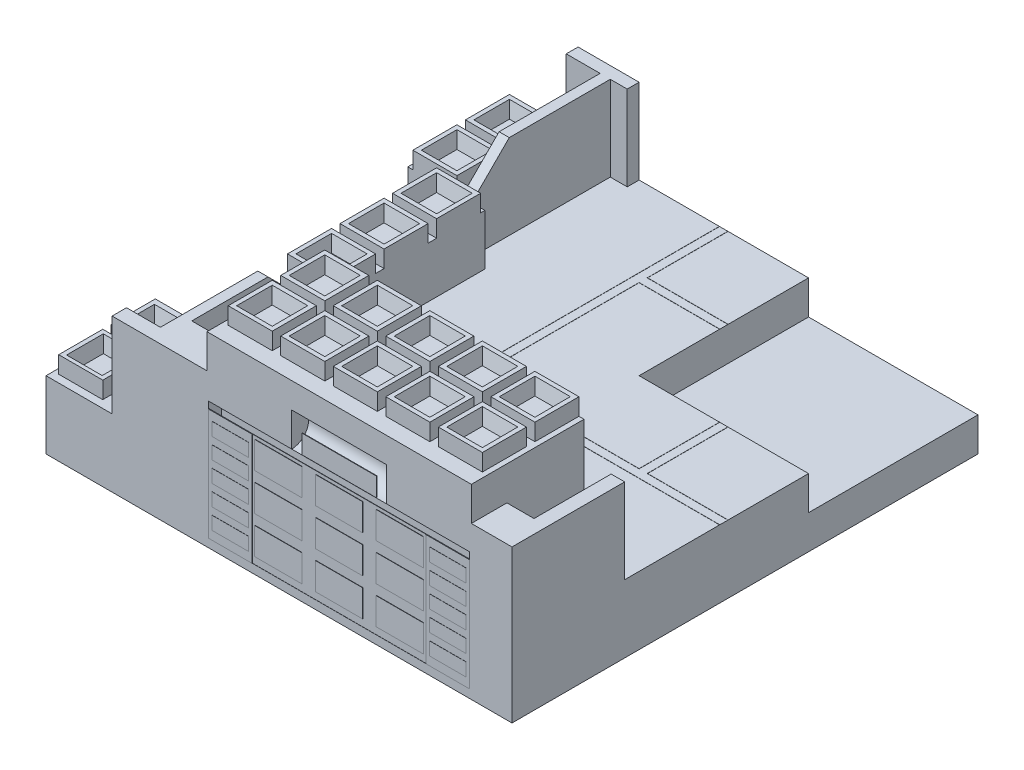
SolidWorks part; units mm, degrees
material "1023 碳钢板 (SS)"
ref_plane "前视基准面" through (0, 0, 0) normal (0, 0, 1) x (1, 0, 0)
ref_plane "上视基准面" through (0, 0, 0) normal (0, 1, 0) x (1, 0, 0)
ref_plane "右视基准面" through (0, 0, 0) normal (1, 0, 0) x (0, 0, -1)
sketch "草图1" plane through (0, 0, 0) normal (0, 1, 0) x (1, 0, 0)
  line L1 (1375, -1375) -> (-1375, -1375)
  line L2 (1375, -1375) -> (1375, 1375)
  line L3 (1375, 1375) -> (-1375, 1375)
  line L4 (-1375, -1375) -> (-1375, 1375)
  line L5 (1375, -1375) -> (-1375, 1375) construction
  line L6 (1375, 1375) -> (-1375, -1375) construction
  point P0 (0, 0)
  dimension "D1" = 2750
  dimension "D2" = 2750
extrude "凸台-拉伸1" add sketch "草图1" along normal blind 200
sketch "草图2" plane through (0, 200, 0) normal (0, 1, 0) x (1, 0, 0)
  line L1 (1375, 1375) -> (375, 1375)
  line L2 (1375, 1375) -> (1375, 375)
  line L3 (1375, 375) -> (375, 375)
  line L4 (375, 1375) -> (375, 375)
  line L8 (-1375, 1375) -> (-1375, -1375)
  line L9 (-1375, -1375) -> (1375, -1375)
  line L10 (1375, -1375) -> (1375, 1375)
  line L11 (1375, 1375) -> (-1375, 1375)
  line L12 (-1375, 1375) -> (-1375, -1375)
  line L13 (-1375, -1375) -> (1375, -1375)
  line L14 (1375, -1375) -> (1375, 1375)
  line L15 (1375, 1375) -> (-1375, 1375)
  line M9 (-1375, 1375) -> (-1375, -1375)
  line M10 (-1375, -1375) -> (1375, -1375)
  line M11 (1375, -1375) -> (1375, 1375)
  line M12 (1375, 1375) -> (-1375, 1375)
  dimension "D1" = 1000
  dimension "D2" = 1000
  dimension "D3" = 0
extrude "凸台-拉伸2" add sketch "草图2" along normal blind 200 contours L4 L3 M12 M9 M10 M11 region at (-133.3333, 200, 133.3333)
sketch "草图4" plane through (0, 0, 0) normal (0, -1, 0) x (1, 0, 0)
  line L0 (-1375, -1375) -> (-1375, 1375) construction
  line L1 (-1375, -760) -> (-885, -760)
  line L2 (-1375, -760) -> (-1375, 760)
  line L3 (-1375, 760) -> (-885, 760)
  line L4 (-885, -760) -> (-885, 760)
  line L5 (-1375, -760) -> (-885, 760) construction
  line L6 (-1375, 760) -> (-885, -760) construction
  line L7 (-1375, 1375) -> (1375, 1375) construction
  point P0 (-1130, 0)
  dimension "D1" = 615
  dimension "D2" = 490
extrude "切除-拉伸2" cut sketch "草图4" against normal blind 1200
sketch "草图6" plane through (0, 400, 0) normal (0, 1, 0) x (1, 0, 0)
  line L0 (-625, 1375) -> (-625, -625) construction
  line L1 (375, 1375) -> (-1375, 1375) construction
  line L2 (-625, -625) -> (1375, -625) construction
  line L3 (-1375, -760) -> (-885, -760) construction
  line L4 (375, 1375) -> (375, 375) construction
  line L5 (-1085, -1020) -> (-1345, -1020)
  line L6 (-1085, -1020) -> (-1085, -760)
  line L7 (-1085, -760) -> (-1345, -760)
  line L8 (1375, 375) -> (375, 375) construction
  line L9 (-885, -760) -> (-885, 760) construction
  line L10 (-1375, 1375) -> (-1375, 760) construction
  line L11 (-885, 760) -> (-1375, 760) construction
  line L12 (-1085, 1020) -> (-1345, 1020)
  line L13 (-1085, 1020) -> (-1085, 760)
  line L14 (-1085, 760) -> (-1345, 760)
  line L15 (-1345, 1020) -> (-1345, 760)
  line L16 (-1085, 1020) -> (-1345, 760) construction
  line L17 (-1085, 760) -> (-1345, 1020) construction
  line L18 (-1345, -1020) -> (-1345, -760)
  line L19 (-1110, 995) -> (-1320, 995)
  line L20 (-1110, 995) -> (-1110, 785)
  line L21 (-1110, 785) -> (-1320, 785)
  line L22 (-1320, 995) -> (-1320, 785)
  line L23 (-1110, 995) -> (-1320, 785) construction
  line L24 (-1110, 785) -> (-1320, 995) construction
  line L25 (-1085, -1020) -> (-1345, -760) construction
  line L26 (-1375, 1045) -> (-927.1578, 1045) construction
  line L27 (-1085, 1070) -> (-1345, 1330) construction
  line L28 (-1085, 1330) -> (-1345, 1070) construction
  line L29 (-1110, 1305) -> (-1320, 1305)
  line L30 (-1085, 1330) -> (-1345, 1330)
  line L31 (-1110, 1305) -> (-1320, 1095) construction
  line L32 (-1110, 1095) -> (-1320, 1305) construction
  line L33 (-1320, 1095) -> (-1320, 1305)
  line L34 (-1110, 1095) -> (-1110, 1305)
  line L35 (-1110, 1095) -> (-1320, 1095)
  line L36 (-1345, 1070) -> (-1345, 1330)
  line L37 (-1085, 1070) -> (-1085, 1330)
  line L38 (-1085, 1070) -> (-1345, 1070)
  line L39 (-1085, -760) -> (-1345, -1020) construction
  line L41 (-755, 1375) -> (-755, -1375) construction
  line L42 (-1375, -1375) -> (1375, -1375) construction
  line L43 (-885, 0) -> (-625, 0) construction
  line L44 (-1085, -1070) -> (-1345, -1070)
  line L45 (-1085, -1070) -> (-1085, -1330)
  line L46 (-1085, -1330) -> (-1345, -1330)
  line L47 (-1345, -1070) -> (-1345, -1330)
  line L48 (-1085, -1070) -> (-1345, -1330) construction
  line L49 (-1085, -1330) -> (-1345, -1070) construction
  line L50 (-1375, -760) -> (-1375, -1375) construction
  point P13 (-1215, 890)
  point P20 (-1215, 890)
  point P32 (-1215, 1200)
  point P33 (-1215, -890)
  point P46 (-755, 0)
  point P51 (-1215, -1200)
  dimension "D1" = 1000
  dimension "D2" = 1000
  dimension "D3" = 200
  dimension "D4" = 30
  dimension "D5" = 260
  dimension "D6" = 210
  dimension "D7" = 310
  dimension "D8" = 260
  dimension "D9" = 30
  dimension "D10" = 310
extrude "凸台-拉伸3" add sketch "草图6" along normal blind 100 contours L38 L36 L30 L37
extrude "凸台-拉伸4" add sketch "草图6<4>" along normal blind 100 contours L13 L14 L15 L12 | L6 L5 L18 L7 | L45 L44 L47 L46
sketch "草图6<4>" plane through (0, 400, 0) normal (0, 1, 0) x (1, 0, 0) same geometry as "草图6"
sketch "草图7" plane through (0, 500, 0) normal (0, 1, 0) x (1, 0, 0)
  line L0 (-1345, 1070) -> (-1345, 1330) construction
  line L1 (-1320, 1095) -> (-1110, 1095)
  line L2 (-1320, 1095) -> (-1320, 1305)
  line L3 (-1320, 1305) -> (-1110, 1305)
  line L4 (-1110, 1095) -> (-1110, 1305)
  line L5 (-1320, 1095) -> (-1110, 1305) construction
  line L6 (-1320, 1305) -> (-1110, 1095) construction
  line L7 (-1085, 1070) -> (-1345, 1070) construction
  line L8 (-1320, 785) -> (-1110, 785)
  line L9 (-1320, 785) -> (-1320, 995)
  line L10 (-1320, 995) -> (-1110, 995)
  line L11 (-1110, 785) -> (-1110, 995)
  line L12 (-1320, 785) -> (-1110, 995) construction
  line L13 (-1320, 995) -> (-1110, 785) construction
  line L14 (-1085, 1020) -> (-1085, 760) construction
  line L15 (-1085, 1020) -> (-1345, 1020) construction
  line L16 (-1345, -890) -> (-1085, -890) construction
  line L17 (-1110, -989.9712) -> (-1320, -989.9712)
  line L18 (-1110, -989.9712) -> (-1110, -790.0288)
  line L19 (-1110, -790.0288) -> (-1320, -790.0288)
  line L20 (-1320, -989.9712) -> (-1320, -790.0288)
  line L21 (-1110, -989.9712) -> (-1320, -790.0288) construction
  line L22 (-1110, -790.0288) -> (-1320, -989.9712) construction
  line L23 (-1110, -1308.4435) -> (-1320, -1308.4435)
  line L24 (-1110, -1308.4435) -> (-1110, -1091.5565)
  line L25 (-1110, -1091.5565) -> (-1320, -1091.5565)
  line L26 (-1320, -1308.4435) -> (-1320, -1091.5565)
  line L27 (-1110, -1308.4435) -> (-1320, -1091.5565) construction
  line L28 (-1110, -1091.5565) -> (-1320, -1308.4435) construction
  line L29 (-1345, -1020) -> (-1345, -760) construction
  line L30 (-1085, -1020) -> (-1085, -760) construction
  line L31 (-1345, -1200) -> (-1085, -1200) construction
  line L32 (-1085, -760) -> (-1345, -760) construction
  line L33 (-1215, -760) -> (-1215, -1020) construction
  line L34 (-1085, -1020) -> (-1345, -1020) construction
  line L35 (-1345, -1070) -> (-1345, -1330) construction
  line L36 (-1085, -1070) -> (-1085, -1330) construction
  line L37 (-1215, -1070) -> (-1215, -1330) construction
  line L38 (-1085, -1070) -> (-1345, -1070) construction
  line L39 (-1085, -1330) -> (-1345, -1330) construction
  point P0 (-1215, 1200)
  point P5 (-1215, -890)
  point P8 (-1345, 1200)
  point P11 (-1215, 1070)
  point P16 (-1215, 890)
  point P19 (-1085, 890)
  point P22 (-1215, 1020)
  point P27 (-1215, -1200)
  point P38 (-1215, -890)
  point P57 (-1215, -1200)
  dimension "D1" = 210
  dimension "D2" = 210
extrude "切除-拉伸3" cut sketch "草图7" against normal blind 80 draft 15 contours L8 L11 L10 L9 | L1 L4 L3 L2 | L8 L11 L10 L9 | L18 L17 L20 L19 | L24 L23 L26 L25 region at (-1215, 500, -1200) region at (-1215, 500, -890)
sketch "草图8" plane through (0, 400, 0) normal (0, 1, 0) x (1, 0, 0)
  line L0 (-885, 0) -> (-625, 0) construction
  line L1 (-885, -760) -> (-885, 760) construction
  line L3 (-625, 1375) -> (-625, -1375) construction
  line L4 (375, 1375) -> (-1375, 1375) construction
  line L5 (-1375, -1375) -> (1375, -1375) construction
  line L6 (375, 1375) -> (375, 375) construction
  line L7 (-755, 457.7919) -> (-755, -449.0399) construction
  line L9 (-625, -130) -> (-885, -130)
  line L10 (-625, -130) -> (-625, 130)
  line L11 (-625, 130) -> (-885, 130)
  line L12 (-885, -130) -> (-885, 130)
  line L13 (-625, -130) -> (-885, 130) construction
  line L14 (-625, 130) -> (-885, -130) construction
  line L15 (-625, -440) -> (-885, -440)
  line L16 (-625, -440) -> (-625, -180)
  line L17 (-625, -180) -> (-885, -180)
  line L18 (-885, -440) -> (-885, -180)
  line L19 (-625, -440) -> (-885, -180) construction
  line L20 (-625, -180) -> (-885, -440) construction
  line L21 (-625, 440) -> (-885, 440)
  line L22 (-625, 440) -> (-625, 180)
  line L23 (-625, 180) -> (-885, 180)
  line L24 (-885, 440) -> (-885, 180)
  line L25 (-625, 440) -> (-885, 180) construction
  line L26 (-625, 180) -> (-885, 440) construction
  point P4 (-755, 0)
  point P17 (-755, 0)
  point P21 (-755, -310)
  point P26 (-755, 310)
  dimension "D1" = 1000
  dimension "D2" = 310
  dimension "D3" = 310
extrude "凸台-拉伸5" add sketch "草图8" along normal blind 400
sketch "草图9" plane through (0, 800, 0) normal (0, 1, 0) x (1, 0, 0)
  line L0 (-885, 440) -> (-625, 180)
  line L1 (-625, 440) -> (-885, 180)
  line L2 (-885, 130) -> (-625, -130)
  line L3 (-625, 130) -> (-885, -130)
  line L4 (-625, -180) -> (-885, -440)
  line L5 (-885, -180) -> (-625, -440)
  line L7 (-650, 205) -> (-860, 205)
  line L8 (-650, 205) -> (-650, 415)
  line L9 (-650, 415) -> (-860, 415)
  line L10 (-860, 205) -> (-860, 415)
  line L11 (-650, 205) -> (-860, 415) construction
  line L12 (-650, 415) -> (-860, 205) construction
  line L13 (-650, -105) -> (-860, -105)
  line L14 (-650, -105) -> (-650, 105)
  line L15 (-650, 105) -> (-860, 105)
  line L16 (-860, -105) -> (-860, 105)
  line L17 (-650, -105) -> (-860, 105) construction
  line L18 (-650, 105) -> (-860, -105) construction
  line L19 (-650, -415) -> (-860, -415)
  line L20 (-650, -415) -> (-650, -205)
  line L21 (-650, -205) -> (-860, -205)
  line L22 (-860, -415) -> (-860, -205)
  line L23 (-650, -415) -> (-860, -205) construction
  line L24 (-650, -205) -> (-860, -415) construction
  point P24 (-755, 310)
  point P29 (-755, 0)
  point P34 (-755, -310)
  dimension "D1" = 210
extrude "切除-拉伸4" cut sketch "草图9" against normal blind 80 draft 15 contours L8 L9 L10 L7 | L14 L15 L16 L13 | L20 L21 L22 L19
sketch "草图11" plane through (0, 400, 0) normal (0, 1, 0) x (1, 0, 0)
  line L0 (-625, -180) -> (-885, -180) construction
  line L1 (-625, -180) -> (-625, -130)
  line L2 (-625, -440) -> (-625, -180) construction
  line L3 (-885, -130) -> (-625, -130) construction
  line L4 (-625, 180) -> (-625, 130)
  line L5 (-625, 180) -> (-625, 440) construction
  line L6 (-885, 180) -> (-625, 180) construction
  line L7 (-625, -130) -> (-625, 130) construction
  line L8 (-625, 130) -> (-885, 130) construction
  line L9 (-885, 180) -> (-885, 130)
  line L10 (-885, 130) -> (-885, 180) construction
  line L11 (-885, 130) -> (-625, 130)
  line L12 (-625, 180) -> (-885, 180)
  line L13 (-885, -130) -> (-625, -130)
  line L14 (-885, -180) -> (-885, -130) construction
  line L15 (-625, -180) -> (-885, -180)
  line L16 (-885, -180) -> (-885, -130)
extrude "凸台-拉伸7" add sketch "草图11" along normal blind 300
sketch "草图14" plane through (0, 400, 0) normal (0, 1, 0) x (1, 0, 0)
  line L0 (-985, 1375) -> (-985, 1305)
  line L1 (375, 1375) -> (-1375, 1375) construction
  line L2 (-785, 1305) -> (-985, 1305)
  line L3 (-785, 1305) -> (-785, 465)
  line L4 (-785, 465) -> (-885, 465)
  line L5 (-885, 440) -> (-885, 760) construction
  line L6 (-1375, 1375) -> (-1375, 760) construction
  line L7 (-625, 440) -> (-885, 440) construction
  line L8 (-625, 440) -> (-625, 552.5193)
  line L9 (-625, -440) -> (-625, 440) construction
  line L10 (-625, 180) -> (-625, 440) construction
  line L11 (-625, 465) -> (-725, 465)
  line L12 (-725, 465) -> (-725, 1305)
  line L13 (-725, 1305) -> (-625, 1305)
  line L14 (-625, 1305) -> (-625, 1375)
  line L15 (-625, 1375) -> (-985, 1375)
  line L16 (-625, 440) -> (-885, 440)
  line L17 (-885, 440) -> (-885, 180) construction
  line L18 (-625, 440) -> (-885, 440) construction
  line L19 (-885, 440) -> (-885, 465)
  line M9 (-885, 440) -> (-625, 440)
  line M23 (375, 1375) -> (-1375, 1375)
  line M30 (-885, 760) -> (-885, 440)
  dimension "D1" = 390
  dimension "D2" = 70
  dimension "D3" = 25
  dimension "D4" = 100
extrude "凸台-拉伸9" add sketch "草图14" along normal blind 500 contours L13 L14 L0 L2 L3 L4 L8 L11 L12 M23 M30 M9 region at (-770.3471, 400, -990.4172)
sketch "草图15" plane through (-625, 0, 0) normal (1, 0, 0) x (0, 0, -1)
  line L0 (440, 800) -> (440, 700)
  line L1 (440, 900) -> (440, 800) construction
  line L2 (440, 700) -> (465, 700)
  line L3 (465, 900) -> (465, 400) construction
  line L4 (465, 700) -> (465, 900)
  line L5 (465, 900) -> (465, 400) construction
  line L6 (440, 900) -> (465, 900) construction
  line L7 (465, 900) -> (440, 900)
  line L8 (440, 900) -> (440, 800)
extrude "切除-拉伸5" cut sketch "草图15" against normal through all
sketch "草图16" plane through (-725, 0, 0) normal (1, 0, 0) x (0, 0, -1)
  line L0 (465, 700) -> (508.8251, 700)
  line L1 (465, 700) -> (465, 400) construction
  line L2 (465, 900) -> (465, 700) construction
  line L3 (508.8251, 700) -> (708.8251, 900)
  line L4 (465, 900) -> (1305, 900) construction
  line L5 (708.8251, 900) -> (465, 900)
  line L6 (465, 900) -> (465, 700)
  dimension "D1" = 45
  dimension "D2" = 200
extrude "切除-拉伸6" cut sketch "草图16" against normal through all
sketch "草图18" plane through (0, 400, 0) normal (0, 1, 0) x (1, 0, 0)
  line L0 (-885, -465) -> (-785, -465)
  line L1 (-885, -760) -> (-885, -440) construction
  line L2 (-785, -465) -> (-785, -1290)
  line L3 (-785, -1290) -> (-985, -1290)
  line L4 (-985, -1290) -> (-985, -1375)
  line L5 (-1375, -1375) -> (1375, -1375) construction
  line L6 (-1375, -760) -> (-1375, -1375) construction
  line L7 (-885, -440) -> (-625, -440) construction
  line L8 (-885, -440) -> (-625, -440)
  line L9 (-625, -440) -> (-625, -465)
  line L10 (-625, -465) -> (-725, -465)
  line L11 (-725, -465) -> (-725, -1165)
  line L12 (-725, -1165) -> (-425, -1165)
  line L13 (-425, -1165) -> (-425, -1375)
  line L14 (-425, -1375) -> (-985, -1375)
  line L15 (-625, -440) -> (-625, 465) construction
  line L16 (-885, -440) -> (-885, -465)
  dimension "D1" = 390
  dimension "D2" = 25
  dimension "D3" = 100
  dimension "D4" = 200
  dimension "D5" = 850
  dimension "D6" = 160
  dimension "D7" = 210
extrude "凸台-拉伸10" add sketch "草图18" along normal blind 500
sketch "草图19" plane through (-625, 0, 0) normal (1, 0, 0) x (0, 0, -1)
  line L0 (-440, 800) -> (-440, 700)
  line L1 (-440, 800) -> (-180, 800) construction
  line L2 (-440, 900) -> (-440, 800) construction
  line L3 (-440, 700) -> (-465, 700)
  line L4 (-465, 900) -> (-465, 400) construction
  line L5 (-465, 700) -> (-465, 900)
  line L6 (-465, 900) -> (-440, 900)
  line L7 (-465, 900) -> (-440, 900) construction
  line L8 (-440, 900) -> (-440, 800)
extrude "切除-拉伸7" cut sketch "草图19" against normal through all
sketch "草图20" plane through (-725, 0, 0) normal (1, 0, 0) x (0, 0, -1)
  line L0 (-465, 700) -> (-515, 700)
  line L1 (-465, 900) -> (-465, 700) construction
  line L2 (-465, 700) -> (-465, 400) construction
  line L3 (-515, 700) -> (-715, 900)
  line L4 (-1165, 900) -> (-465, 900) construction
  line L5 (-715, 900) -> (-465, 900)
  line L6 (-465, 900) -> (-465, 700)
  dimension "D1" = 200
  dimension "D2" = 45
  dimension "D3" = 50
extrude "切除-拉伸8" cut sketch "草图20" against normal through all
sketch "草图28" plane through (0, 400, 0) normal (0, 1, 0) x (1, 0, 0)
  line L0 (-425, -1375) -> (-425, -710)
  line L1 (-425, -710) -> (1105, -710)
  line L2 (1105, -710) -> (1105, -1375)
  line L3 (-265, -765.1076) -> (-265, -988.6758) construction
  line L4 (1375, -1375) -> (1375, 375) construction
  line L5 (-625, -465) -> (-625, 465) construction
  line L6 (-725, -465) -> (-625, -465) construction
  line L7 (175, -969.7166) -> (-85, -709.7166) construction
  line L8 (-135, -969.7166) -> (-395, -969.7166)
  line L9 (-135, -969.7166) -> (-135, -709.7166)
  line L10 (-135, -709.7166) -> (-395, -709.7166)
  line L11 (-395, -969.7166) -> (-395, -709.7166)
  line L12 (-135, -969.7166) -> (-395, -709.7166) construction
  line L13 (-135, -709.7166) -> (-395, -969.7166) construction
  line L14 (175, -709.7166) -> (-85, -969.7166) construction
  line L15 (175, -969.7166) -> (175, -709.7166)
  line L16 (175, -969.7166) -> (-85, -969.7166)
  line L17 (-85, -969.7166) -> (-85, -709.7166)
  line L18 (175, -709.7166) -> (-85, -709.7166)
  line L19 (485, -969.7166) -> (225, -709.7166) construction
  line L20 (485, -709.7166) -> (225, -969.7166) construction
  line L21 (485, -969.7166) -> (485, -709.7166)
  line L22 (485, -969.7166) -> (225, -969.7166)
  line L23 (225, -969.7166) -> (225, -709.7166)
  line L24 (485, -709.7166) -> (225, -709.7166)
  line L25 (795, -969.7166) -> (535, -709.7166) construction
  line L26 (795, -709.7166) -> (535, -969.7166) construction
  line L27 (795, -969.7166) -> (795, -709.7166)
  line L28 (795, -969.7166) -> (535, -969.7166)
  line L29 (535, -969.7166) -> (535, -709.7166)
  line L30 (795, -709.7166) -> (535, -709.7166)
  line L31 (1105, -969.7166) -> (845, -709.7166) construction
  line L32 (1105, -709.7166) -> (845, -969.7166) construction
  line L33 (1105, -969.7166) -> (1105, -709.7166)
  line L34 (1105, -969.7166) -> (845, -969.7166)
  line L35 (845, -969.7166) -> (845, -709.7166)
  line L36 (1105, -709.7166) -> (845, -709.7166)
  line L37 (175, -1279.7166) -> (-85, -1019.7166) construction
  line L38 (175, -1019.7166) -> (-85, -1279.7166) construction
  line L39 (175, -1279.7166) -> (175, -1019.7166)
  line L40 (175, -1279.7166) -> (-85, -1279.7166)
  line L41 (-85, -1279.7166) -> (-85, -1019.7166)
  line L42 (175, -1019.7166) -> (-85, -1019.7166)
  line L43 (485, -1279.7166) -> (225, -1019.7166) construction
  line L44 (485, -1019.7166) -> (225, -1279.7166) construction
  line L45 (485, -1279.7166) -> (485, -1019.7166)
  line L46 (485, -1279.7166) -> (225, -1279.7166)
  line L47 (225, -1279.7166) -> (225, -1019.7166)
  line L48 (485, -1019.7166) -> (225, -1019.7166)
  line L49 (795, -1279.7166) -> (535, -1019.7166) construction
  line L50 (795, -1019.7166) -> (535, -1279.7166) construction
  line L51 (795, -1279.7166) -> (795, -1019.7166)
  line L52 (795, -1279.7166) -> (535, -1279.7166)
  line L53 (535, -1279.7166) -> (535, -1019.7166)
  line L54 (795, -1019.7166) -> (535, -1019.7166)
  line L55 (1105, -1279.7166) -> (845, -1019.7166) construction
  line L56 (1105, -1019.7166) -> (845, -1279.7166) construction
  line L57 (1105, -1279.7166) -> (1105, -1019.7166)
  line L58 (1105, -1279.7166) -> (845, -1279.7166)
  line L59 (845, -1279.7166) -> (845, -1019.7166)
  line L60 (1105, -1019.7166) -> (845, -1019.7166)
  line L61 (-135, -1279.7166) -> (-395, -1019.7166) construction
  line L62 (-135, -1019.7166) -> (-395, -1279.7166) construction
  line L63 (-135, -1279.7166) -> (-135, -1019.7166)
  line L64 (-135, -1279.7166) -> (-395, -1279.7166)
  line L65 (-395, -1279.7166) -> (-395, -1019.7166)
  line L66 (-135, -1019.7166) -> (-395, -1019.7166)
  line L68 (1105, -710) -> (1135, -710)
  line L69 (1105, -710) -> (1105, -1375)
  line L70 (1105, -1375) -> (1135, -1375)
  line L71 (1135, -710) -> (1135, -1375)
  point P12 (-265, -839.7166)
  point P20 (45, -839.7166)
  point P25 (355, -839.7166)
  point P30 (665, -839.7166)
  point P35 (975, -839.7166)
  point P40 (45, -1149.7166)
  point P45 (355, -1149.7166)
  point P50 (665, -1149.7166)
  point P55 (975, -1149.7166)
  point P60 (-265, -1149.7166)
  line M9 (-425, -1165) -> (-425, -1375)
  line M10 (-425, -1375) -> (1375, -1375)
  dimension "D1" = 270
  dimension "D2" = 200
  dimension "D3" = 245
  dimension "D4" = 1640
  dimension "D5" = 5
  dimension "D6" = 2
extrude "凸台-拉伸14" add sketch "草图28" along normal blind 700 contours L60 L2 L34 L35 L1 L27 L28 L29 L21 L22 L23 L15 L16 L17 L9 L8 L11 L0 L58 L59 L66 L63 L64 L65 L54 L51 L52 L53 L48 L45 L46 L47 L42 L39 L40 L41 M9 M10 | L68 L71 L70 L69 region at (-408.3173, 400, 1270)
extrude "凸台-拉伸15" add sketch "草图28<3>" along normal blind 800 contours L11 L8 L9 L1 | L63 L66 L65 L64 | L17 L16 L15 L1 | L23 L22 L21 L1 | L45 L48 L47 L46 | L29 L28 L27 L1 | L51 L54 L53 L52 | L39 L42 L41 L40 | L35 L34 L2 L1 | L2 L60 L59 L58 region at (-265, 400, 839.8583) region at (975, 400, 839.8583) region at (665, 400, 839.8583) region at (355, 400, 839.8583) region at (45, 400, 839.8583) region at (975, 400, 1149.7166) region at (45, 400, 1149.7166) region at (355, 400, 1149.7166) region at (665, 400, 1149.7166) region at (-265, 400, 1149.7166)
sketch "草图28<3>" plane through (0, 400, 0) normal (0, 1, 0) x (1, 0, 0) same geometry as "草图28"
sketch "草图30" plane through (0, 1200, 0) normal (0, 1, 0) x (1, 0, 0)
  line L0 (150, -944.856) -> (-60, -734.8583) construction
  line L1 (-160, -944.856) -> (-370, -944.8583)
  line L2 (-160, -944.856) -> (-160.9849, -734.8583)
  line L3 (-160.9849, -734.8583) -> (-370, -734.8583)
  line L4 (-370, -944.8583) -> (-370, -734.8583)
  line L5 (-160, -944.856) -> (-370, -734.8583) construction
  line L6 (-160.9849, -734.8583) -> (-370, -944.8583) construction
  line L7 (149.0151, -734.8583) -> (-60, -944.8583) construction
  line L8 (150, -944.856) -> (149.0151, -734.8583)
  line L9 (150, -944.856) -> (-60, -944.8583)
  line L10 (-60, -944.8583) -> (-60, -734.8583)
  line L11 (149.0151, -734.8583) -> (-60, -734.8583)
  line L12 (460, -944.856) -> (250, -734.8583) construction
  line L13 (459.0151, -734.8583) -> (250, -944.8583) construction
  line L14 (460, -944.856) -> (459.0151, -734.8583)
  line L15 (460, -944.856) -> (250, -944.8583)
  line L16 (250, -944.8583) -> (250, -734.8583)
  line L17 (459.0151, -734.8583) -> (250, -734.8583)
  line L18 (770, -944.856) -> (560, -734.8583) construction
  line L19 (769.0151, -734.8583) -> (560, -944.8583) construction
  line L20 (770, -944.856) -> (769.0151, -734.8583)
  line L21 (770, -944.856) -> (560, -944.8583)
  line L22 (560, -944.8583) -> (560, -734.8583)
  line L23 (769.0151, -734.8583) -> (560, -734.8583)
  line L24 (1080, -944.856) -> (870, -734.8583) construction
  line L25 (1079.0151, -734.8583) -> (870, -944.8583) construction
  line L26 (1080, -944.856) -> (1079.0151, -734.8583)
  line L27 (1080, -944.856) -> (870, -944.8583)
  line L28 (870, -944.8583) -> (870, -734.8583)
  line L29 (1079.0151, -734.8583) -> (870, -734.8583)
  line L30 (150, -1254.856) -> (-60, -1044.8583) construction
  line L31 (149.0151, -1044.8583) -> (-60, -1254.8583) construction
  line L32 (150, -1254.856) -> (149.0151, -1044.8583)
  line L33 (150, -1254.856) -> (-60, -1254.8583)
  line L34 (-60, -1254.8583) -> (-60, -1044.8583)
  line L35 (149.0151, -1044.8583) -> (-60, -1044.8583)
  line L36 (460, -1254.856) -> (250, -1044.8583) construction
  line L37 (459.0151, -1044.8583) -> (250, -1254.8583) construction
  line L38 (460, -1254.856) -> (459.0151, -1044.8583)
  line L39 (460, -1254.856) -> (250, -1254.8583)
  line L40 (250, -1254.8583) -> (250, -1044.8583)
  line L41 (459.0151, -1044.8583) -> (250, -1044.8583)
  line L42 (770, -1254.856) -> (560, -1044.8583) construction
  line L43 (769.0151, -1044.8583) -> (560, -1254.8583) construction
  line L44 (770, -1254.856) -> (769.0151, -1044.8583)
  line L45 (770, -1254.856) -> (560, -1254.8583)
  line L46 (560, -1254.8583) -> (560, -1044.8583)
  line L47 (769.0151, -1044.8583) -> (560, -1044.8583)
  line L48 (1080, -1254.856) -> (870, -1044.8583) construction
  line L49 (1079.0151, -1044.8583) -> (870, -1254.8583) construction
  line L50 (1080, -1254.856) -> (1079.0151, -1044.8583)
  line L51 (1080, -1254.856) -> (870, -1254.8583)
  line L52 (870, -1254.8583) -> (870, -1044.8583)
  line L53 (1079.0151, -1044.8583) -> (870, -1044.8583)
  line L54 (-160, -1254.856) -> (-370, -1044.8583) construction
  line L55 (-160.9849, -1044.8583) -> (-370, -1254.8583) construction
  line L56 (-160, -1254.856) -> (-160.9849, -1044.8583)
  line L57 (-160, -1254.856) -> (-370, -1254.8583)
  line L58 (-370, -1254.8583) -> (-370, -1044.8583)
  line L59 (-160.9849, -1044.8583) -> (-370, -1044.8583)
  point P0 (-265, -839.8583)
  point P8 (45, -839.8583)
  point P13 (355, -839.8583)
  point P18 (665, -839.8583)
  point P23 (975, -839.8583)
  point P28 (45, -1149.8583)
  point P33 (355, -1149.8583)
  point P38 (665, -1149.8583)
  point P43 (975, -1149.8583)
  point P48 (-265, -1149.8583)
  dimension "D1" = 5
  dimension "D2" = 2
extrude "切除-拉伸10" cut sketch "草图30" against normal blind 80 draft 15
sketch "草图32" plane through (0, 400, 0) normal (0, 1, 0) x (1, 0, 0)
  line L0 (1135, -1165) -> (1295, -1165)
  line L1 (1295, -1165) -> (1295, -710)
  line L2 (1295, -710) -> (1375, -710)
  line L3 (1135, -1375) -> (1375, -1375) construction
  line L4 (1375, -1375) -> (1375, 375) construction
  line L5 (1375, -710) -> (1375, -1375)
  line L6 (1375, -1375) -> (1135, -1375)
  line L7 (1135, -1375) -> (1135, -1165)
  dimension "D1" = 665
  dimension "D2" = 210
  dimension "D3" = 80
extrude "凸台-拉伸17" add sketch "草图32" along normal blind 500
sketch "草图34" plane through (0, 0, 1375) normal (0, 0, 1) x (1, 0, 0)
  line L0 (-1375, 50) -> (1375, 50) construction
  line L1 (-1375, 0) -> (1375, 0) construction
  line L2 (355, 1100) -> (355, 0) construction
  line L3 (1375, 900) -> (1375, 0) construction
  line L4 (-425, 1100) -> (-425, 900) construction
  line L5 (1125, 50) -> (-415, 50)
  line L6 (1125, 50) -> (1125, 750)
  line L7 (1125, 750) -> (-415, 750)
  line L8 (-415, 50) -> (-415, 750)
  line L9 (1135, 1100) -> (1135, 900) construction
  dimension "D1" = 50
  dimension "D2" = 1020
  dimension "D3" = 10
  dimension "D4" = 10
  dimension "D5" = 700
extrude "切除-拉伸11" cut sketch "草图34" against normal blind 70 draft 5
sketch "草图35" plane through (0, 0, 1375) normal (0, 0, 1) x (1, 0, 0)
  line L0 (-425, 1100) -> (-425, 900) construction
  line L1 (75, 750) -> (635, 750)
  line L2 (75, 750) -> (75, 850)
  line L3 (75, 850) -> (635, 850)
  line L4 (635, 750) -> (635, 850)
  line L5 (1135, 1100) -> (1135, 900) construction
  line L7 (-425, 1100) -> (1135, 1100) construction
  point P6 (75, 800)
  dimension "D1" = 500
  dimension "D2" = 500
  dimension "D3" = 350
  dimension "D4" = 250
revolve "切除-旋转1" cut sketch "草图35" angle 180 about L3
ref_plane "基准面14" through (0, 0, 1374) normal (0, 0, 1) x (1, 0, 0)
sketch "草图36" plane through (0, 0, 1374) normal (0, 0, 1) x (1, 0, 0)
  line L0 (355, 1039.0609) -> (355, -144.8774) construction
  line L1 (-415, 710) -> (1125, 710) construction
  line L3 (216.0298, 691.1879) -> (216.0298, 532.1001)
  line L4 (-415, 710) -> (-158.5057, 710)
  line L5 (-415, 710) -> (-415, 50)
  line L6 (-415, 50) -> (-158.5057, 50)
  line L7 (-158.5057, 710) -> (-158.5057, 50)
  line L8 (-142.5111, 691.1879) -> (135.4292, 691.1879)
  line L9 (-142.5111, 691.1879) -> (-142.5111, 532.1001)
  line L10 (-142.5111, 532.1001) -> (135.4292, 532.1001)
  line L11 (135.4292, 691.1879) -> (135.4292, 532.1001)
  line L12 (216.0298, 691.1879) -> (493.9702, 691.1879)
  line L13 (493.9702, 691.1879) -> (493.9702, 532.1001)
  line L14 (216.0298, 532.1001) -> (493.9702, 532.1001)
  line L15 (574.5708, 691.1879) -> (574.5708, 532.1001)
  line L16 (574.5708, 691.1879) -> (852.5111, 691.1879)
  line L17 (852.5111, 691.1879) -> (852.5111, 532.1001)
  line L18 (574.5708, 532.1001) -> (852.5111, 532.1001)
  line L19 (216.0298, 471.1879) -> (216.0298, 312.1001)
  line L20 (216.0298, 471.1879) -> (493.9702, 471.1879)
  line L21 (493.9702, 471.1879) -> (493.9702, 312.1001)
  line L22 (216.0298, 312.1001) -> (493.9702, 312.1001)
  line L23 (574.5708, 471.1879) -> (574.5708, 312.1001)
  line L24 (574.5708, 471.1879) -> (852.5111, 471.1879)
  line L25 (852.5111, 471.1879) -> (852.5111, 312.1001)
  line L26 (574.5708, 312.1001) -> (852.5111, 312.1001)
  line L27 (216.0298, 251.1879) -> (216.0298, 92.1001)
  line L28 (216.0298, 251.1879) -> (493.9702, 251.1879)
  line L29 (493.9702, 251.1879) -> (493.9702, 92.1001)
  line L30 (216.0298, 92.1001) -> (493.9702, 92.1001)
  line L31 (574.5708, 251.1879) -> (574.5708, 92.1001)
  line L32 (574.5708, 251.1879) -> (852.5111, 251.1879)
  line L33 (852.5111, 251.1879) -> (852.5111, 92.1001)
  line L34 (574.5708, 92.1001) -> (852.5111, 92.1001)
  line L35 (-142.5111, 471.1879) -> (-142.5111, 312.1001)
  line L36 (-142.5111, 471.1879) -> (135.4292, 471.1879)
  line L37 (135.4292, 471.1879) -> (135.4292, 312.1001)
  line L38 (-142.5111, 312.1001) -> (135.4292, 312.1001)
  line L39 (-142.5111, 251.1879) -> (-142.5111, 92.1001)
  line L40 (-142.5111, 251.1879) -> (135.4292, 251.1879)
  line L41 (135.4292, 251.1879) -> (135.4292, 92.1001)
  line L42 (-142.5111, 92.1001) -> (135.4292, 92.1001)
  line L43 (1125, 50) -> (868.5057, 50)
  line L44 (868.5057, 710) -> (868.5057, 50)
  line L45 (1125, 710) -> (868.5057, 710)
  line L46 (1125, 710) -> (1125, 50)
  line L47 (75, 950) -> (635, 950) construction
  point P48 (355, 691.1879)
  point P51 (355, 950)
  dimension "D2" = 3
  dimension "D3" = 3
extrude "凸台-拉伸18" add sketch "草图36" along normal blind 2
sketch "草图38" plane through (0, 0, 1374) normal (0, 0, 1) x (1, 0, 0)
  line L1 (-158.5057, 710) -> (-415, 710) construction
  line L2 (1125, 710) -> (868.5057, 710) construction
  line L3 (868.5057, 50) -> (1125, 50) construction
  line L4 (-415, 50) -> (-158.5057, 50) construction
  line L5 (-158.5057, 50) -> (868.5057, 50) construction
  line L6 (-415, 710) -> (-415, 50) construction
  line L7 (1125, 50) -> (1125, 710) construction
  line L8 (-158.5057, 710) -> (-415, 710)
  line L9 (1125, 710) -> (868.5057, 710)
  line L10 (868.5057, 50) -> (1125, 50)
  line L11 (-415, 50) -> (-158.5057, 50)
  line L12 (-158.5057, 50) -> (868.5057, 50)
  line L13 (-415, 710) -> (-415, 50)
  line L14 (1125, 50) -> (1125, 710)
  line L15 (-158.5057, 710) -> (868.5057, 710)
extrude "凸台-拉伸19" add sketch "草图38" against normal blind 2
sketch "草图39" plane through (0, 0, 1374) normal (0, 0, 1) x (1, 0, 0)
  line L0 (135.8051, 860.9296) -> (135.8051, 750)
  line L1 (135.8051, 860.9296) -> (574.1949, 860.9296)
  line L2 (135.8051, 750) -> (574.1949, 750)
  line L3 (574.1949, 860.9296) -> (574.1949, 750)
  line L4 (135.8051, 860.9296) -> (574.1949, 750) construction
  line L5 (135.8051, 750) -> (574.1949, 860.9296) construction
  point P1 (355, 805.4648)
extrude "凸台-拉伸20" add sketch "草图39" against normal blind 3
sketch "草图41" plane through (0, 400, 0) normal (0, 1, 0) x (1, 0, 0)
  line L0 (400, -150) -> (1375, -150)
  line L1 (-625, -26) -> (-151, -26)
  line L2 (-150, -125) -> (-246.1645, -125) construction
  line L3 (1375, 1375) -> (375, 1375) construction
  line L4 (-150, 1375) -> (-150, 24)
  line L5 (-100, 1375) -> (-100, 900)
  line L6 (-100, 875) -> (375, 875) construction
  line L7 (-625, 24) -> (-150, 24)
  line L8 (-100, 900) -> (375, 900)
  line L9 (-100, 850) -> (375, 850)
  line L10 (-625, 0) -> (-150, 0) construction
  line L11 (-625, -130) -> (-625, 130) construction
  line L12 (-625, 25) -> (-151, 25)
  line L13 (-625, -25) -> (-150, -25)
  line L14 (-100, 850) -> (-100, -70)
  line L15 (-625, -25) -> (-625, -26)
  line L16 (850, 375) -> (850, -100)
  line L17 (-150, -25) -> (-150, -26)
  line L18 (-625, 25) -> (-625, 24)
  line L19 (900, 375) -> (900, -100)
  line L20 (-70, -100) -> (850, -100)
  line L21 (-120, -150) -> (350, -150)
  line L22 (375, -150) -> (375, -632.5868) construction
  line L23 (350, -150) -> (350, -710)
  line L24 (375, 1375) -> (375, 375) construction
  line L25 (400, -150) -> (400, -710)
  line L26 (900, -100) -> (1375, -100)
  line L27 (-150, 25) -> (-150, 24)
  line L28 (-151, 1375) -> (-151, 25)
  line L29 (-120, -151) -> (349, -151)
  line L30 (349, -151) -> (349, -710)
  line L31 (-101, 851) -> (375, 851)
  line L32 (-101, 851) -> (-101, -70)
  line L33 (-70, -101) -> (851, -101)
  line L34 (851, 375) -> (851, -101)
  line L35 (-101, 1375) -> (-101, 899)
  line L36 (-101, 899) -> (375, 899)
  line L37 (399, -149) -> (1375, -149)
  line L38 (399, -149) -> (399, -710)
  line L39 (899, 375) -> (899, -101)
  line L40 (899, -101) -> (1375, -101)
  line L41 (-150, 1375) -> (-151, 1375)
  line L42 (350, -710) -> (349, -710)
  line L43 (375, 850) -> (375, 851)
  line L44 (850, 375) -> (851, 375)
  line L45 (-100, 1375) -> (-101, 1375)
  line L46 (375, 900) -> (375, 899)
  line L47 (1375, -150) -> (1375, -149)
  line L48 (400, -710) -> (399, -710)
  line L49 (900, 375) -> (899, 375)
  line L50 (1375, -100) -> (1375, -101)
  line L51 (-151, -26) -> (-151, -120)
  line L52 (-151, 1375) -> (-151, -120) construction
  line L53 (-150, -25) -> (-150, -120)
  line L54 (-150, 1375) -> (-150, -120) construction
  line L55 (-625, -26) -> (-150, -26) construction
  line L56 (-625, 25) -> (-150, 25) construction
  arc A0 (-120, -150) -> (-150, -120) centre (-120, -120) cw
  arc A1 (-70, -100) -> (-100, -70) centre (-70, -70) cw
  arc A2 (-120, -151) -> (-151, -120) centre (-120, -120) cw
  arc A3 (-70, -101) -> (-101, -70) centre (-70, -70) cw
  point P24 (-625, 0)
  line M20 (1375, -710) -> (1375, 375)
  line M21 (1375, 375) -> (375, 375)
  line M23 (375, 1375) -> (-625, 1375)
  line M28 (-625, 465) -> (-625, -465)
  line M33 (-425, -710) -> (1135, -710)
  dimension "D1" = 30
  dimension "D2" = 1500
  dimension "D3" = 25
  dimension "D4" = 1
  dimension "D5" = 25
  dimension "D6" = 1
  dimension "D7" = 25
extrude "凸台-拉伸21" add sketch "草图41" along normal blind 1 contours A2 L29 L30 L23 L21 A0 L53 L17 L13 L1 L51 M33 M28 | L28 L12 L7 L4 M23 M28 | L37 L38 L25 L0 M33 M20 | L39 L40 L26 L19 M20 M21 | L32 A3 L33 L34 L44 L16 L20 A1 L14 L9 L43 L31 | L35 L36 L46 L8 L5 L45 region at (399.5, 400, 698.7426) region at (-610.6793, 400, -24.5) region at (349.5, 400, 698.0843) region at (1137, 400, 100.3268)
sketch "草图42" plane through (0, 0, 1376) normal (0, 0, 1) x (1, 0, 0)
  line L0 (-286.7529, 710) -> (-286.7529, 50) construction
  line L1 (-415, 380) -> (-158.5057, 380) construction
  line L2 (-394.2413, 538.5848) -> (-394.2413, 461.4152)
  line L3 (-394.2413, 418.5848) -> (-179.2644, 418.5848)
  line L4 (-394.2413, 418.5848) -> (-394.2413, 341.4152)
  line L5 (-394.2413, 341.4152) -> (-179.2644, 341.4152)
  line L6 (-179.2644, 418.5848) -> (-179.2644, 341.4152)
  line L7 (-394.2413, 538.5848) -> (-179.2644, 538.5848)
  line L8 (-179.2644, 538.5848) -> (-179.2644, 461.4152)
  line L9 (-394.2413, 461.4152) -> (-179.2644, 461.4152)
  line L10 (-394.2413, 658.5848) -> (-394.2413, 581.4152)
  line L11 (-394.2413, 658.5848) -> (-179.2644, 658.5848)
  line L12 (-179.2644, 658.5848) -> (-179.2644, 581.4152)
  line L13 (-394.2413, 581.4152) -> (-179.2644, 581.4152)
  line L14 (-394.2413, 298.5848) -> (-394.2413, 221.4152)
  line L15 (-394.2413, 298.5848) -> (-179.2644, 298.5848)
  line L16 (-179.2644, 298.5848) -> (-179.2644, 221.4152)
  line L17 (-394.2413, 221.4152) -> (-179.2644, 221.4152)
  line L18 (-394.2413, 178.5848) -> (-394.2413, 101.4152)
  line L19 (-394.2413, 178.5848) -> (-179.2644, 178.5848)
  line L20 (-179.2644, 178.5848) -> (-179.2644, 101.4152)
  line L21 (-394.2413, 101.4152) -> (-179.2644, 101.4152)
  line L22 (355, 750) -> (355, -148.8335) construction
  line L23 (1104.2413, 178.5848) -> (889.2644, 178.5848)
  line L24 (889.2644, 178.5848) -> (889.2644, 101.4152)
  line L25 (1104.2413, 101.4152) -> (889.2644, 101.4152)
  line L26 (1104.2413, 178.5848) -> (1104.2413, 101.4152)
  line L27 (1104.2413, 298.5848) -> (889.2644, 298.5848)
  line L28 (889.2644, 298.5848) -> (889.2644, 221.4152)
  line L29 (1104.2413, 221.4152) -> (889.2644, 221.4152)
  line L30 (1104.2413, 298.5848) -> (1104.2413, 221.4152)
  line L31 (1104.2413, 341.4152) -> (889.2644, 341.4152)
  line L32 (1104.2413, 538.5848) -> (889.2644, 538.5848)
  line L33 (889.2644, 538.5848) -> (889.2644, 461.4152)
  line L34 (1104.2413, 461.4152) -> (889.2644, 461.4152)
  line L35 (1104.2413, 538.5848) -> (1104.2413, 461.4152)
  line L36 (1104.2413, 658.5848) -> (889.2644, 658.5848)
  line L37 (889.2644, 658.5848) -> (889.2644, 581.4152)
  line L38 (1104.2413, 581.4152) -> (889.2644, 581.4152)
  line L39 (1104.2413, 658.5848) -> (1104.2413, 581.4152)
  line L40 (1104.2413, 418.5848) -> (1104.2413, 341.4152)
  line L41 (889.2644, 418.5848) -> (889.2644, 341.4152)
  line L42 (1104.2413, 418.5848) -> (889.2644, 418.5848)
  point P8 (-179.2644, 380)
  point P9 (-286.7529, 418.5848)
  dimension "D1" = 3
  dimension "D2" = 3
extrude "凸台-拉伸22" add sketch "草图42" along normal blind 1
